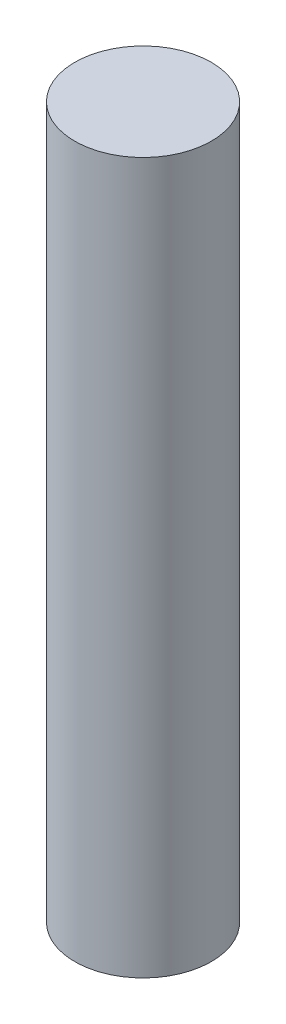
SolidWorks part; units mm, degrees
material "6061-T4 (SS)"
ref_plane "Front Plane" through (0, 0, 0) normal (0, 0, 1) x (1, 0, 0)
ref_plane "Top Plane" through (0, 0, 0) normal (0, 1, 0) x (1, 0, 0)
ref_plane "Right Plane" through (0, 0, 0) normal (1, 0, 0) x (0, 0, -1)
sketch "Sketch1" plane through (0, 0, 0) normal (0, 1, 0) x (1, 0, 0)
  circle A0 centre (0, 0) radius 10
  dimension "D1" = 20
extrude "Boss-Extrude1" add sketch "Sketch1" along normal blind 104
equation "\"D1@Boss-Extrude1\"=104"
